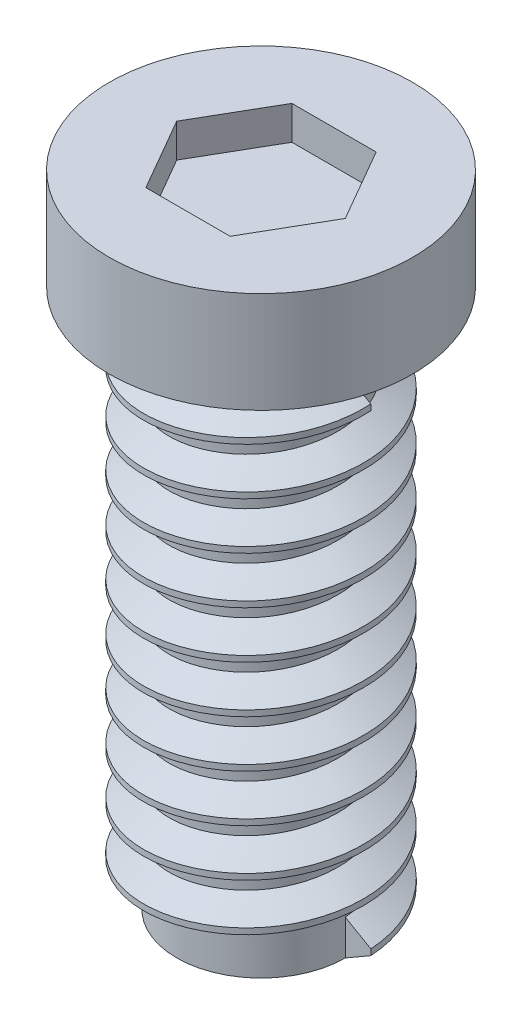
SolidWorks part; units mm, degrees
ref_plane "Front Plane" through (0, 0, 0) normal (0, 0, 1) x (1, 0, 0)
ref_plane "Top Plane" through (0, 0, 0) normal (0, 1, 0) x (1, 0, 0)
ref_plane "Right Plane" through (0, 0, 0) normal (1, 0, 0) x (0, 0, -1)
sketch "Sketch1" plane through (0, 0, 0) normal (0, 1, 0) x (1, 0, 0)
  circle A0 centre (0, 0) radius 1.25
  dimension "D1" = 2.5
extrude "Boss-Extrude1" add sketch "Sketch1" along normal blind 8
sketch "Sketch4" plane through (0, 8, 0) normal (0, 1, 0) x (1, 0, 0)
  circle A0 centre (0, 0) radius 2.25
  dimension "D1" = 4.5
extrude "Boss-Extrude2" add sketch "Sketch4" along normal blind 1.5
sketch "Sketch5" plane through (0, 9.5, 0) normal (0, 1, 0) x (1, 0, 0)
  line L1 (1.25, 0) -> (0.625, 1.0825)
  line L2 (0.625, 1.0825) -> (-0.625, 1.0825)
  line L3 (-0.625, 1.0825) -> (-1.25, 0)
  line L4 (-1.25, 0) -> (-0.625, -1.0825)
  line L5 (-0.625, -1.0825) -> (0.625, -1.0825)
  line L6 (0.625, -1.0825) -> (1.25, 0)
  circle A0 centre (0, 0) radius 1.0825 construction
  dimension "D1" = 1.25
extrude "Cut-Extrude1" cut sketch "Sketch5" against normal blind 0.5
thread "Thread1" pitch 0.7 method extrude profile "Thread Profile1" start angle 0, offset 0, length 7, pitch 0.7, diameter 2.5
ref_plane "Plane1" through (1.25, 0, 0) normal (0, 0, 1) x (1, 0, 0)
sketch "Thread Profile1" plane through (1.25, 0, 0) normal (0, 0, 1) x (1, 0, 0)
  line L0 (0, 0) -> (0, 0.7) construction
  line L1 (0, 0) -> (0.3789, 0.2187)
  line L2 (0.3789, 0.2187) -> (0.3789, 0.3062)
  line L3 (0.3789, 0.3062) -> (0, 0.525)
  line L4 (0.3789, 0.2625) -> (0, 0.2625) construction
  line L11 (0, 0) -> (0, 0.525)
  point P2 (0, 0)
  dimension "Pitch" = 0.7
  dimension "Profile_Angle" = 60
  dimension "Profile_Land" = 0.0875
  dimension "Profile_Height" = 0.3789
